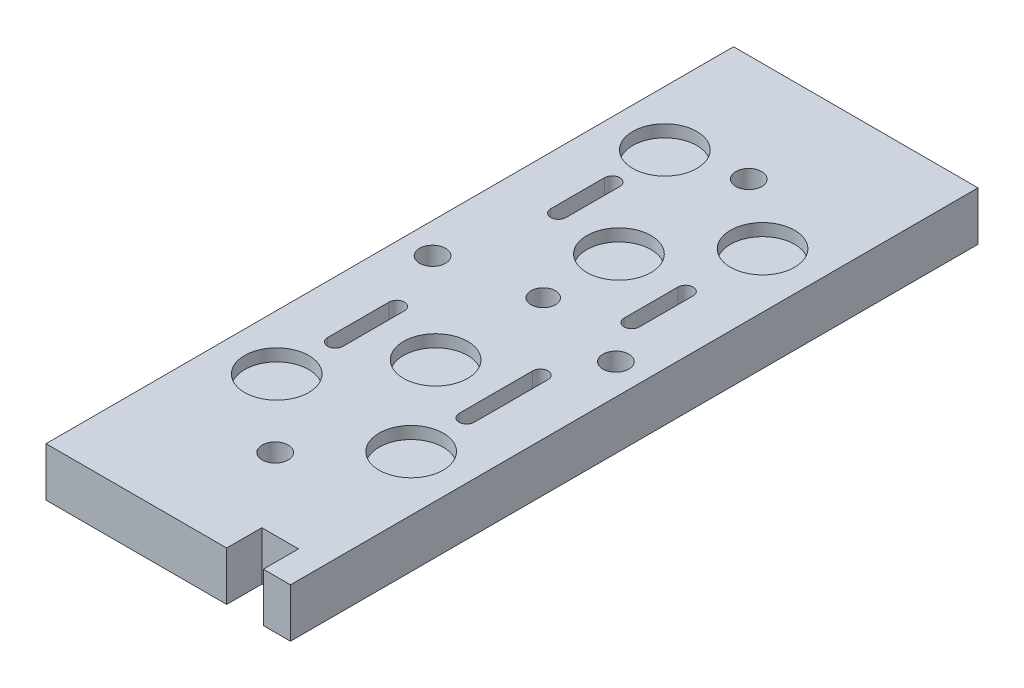
SolidWorks part; units mm, degrees
material "Plain Carbon Steel"
ref_plane "Front Plane" through (0, 0, 0) normal (0, 0, 1) x (1, 0, 0)
ref_plane "Top Plane" through (0, 0, 0) normal (0, 1, 0) x (1, 0, 0)
ref_plane "Right Plane" through (0, 0, 0) normal (1, 0, 0) x (0, 0, -1)
sketch "Sketch1" plane through (0, 0, 0) normal (0, 1, 0) x (1, 0, 0)
  line L1 (-40, -112.5) -> (40, -112.5)
  line L2 (-40, -112.5) -> (-40, 112.5)
  line L3 (-40, 112.5) -> (40, 112.5)
  line L4 (40, -112.5) -> (40, 112.5)
  line L5 (-40, -112.5) -> (40, 112.5) construction
  line L6 (-40, 112.5) -> (40, -112.5) construction
  point P0 (0, 0)
  dimension "D1" = 225
  dimension "D2" = 80
extrude "Boss-Extrude1" add sketch "Sketch1" against normal blind 16
sketch "Sketch2" plane through (0, 0, 0) normal (0, 1, 0) x (1, 0, 0)
  line L4 (24, 17.68) -> (24, 35.28)
  line L5 (19, 35.28) -> (19, 17.68)
  line L6 (24, 17.68) -> (24, 35.28)
  line L7 (19, 35.28) -> (19, 17.68)
  line L10 (24, -36.32) -> (24, -12.22)
  line L11 (19, -12.22) -> (19, -36.32)
  line L12 (24, -36.32) -> (24, -12.22)
  line L13 (19, -12.22) -> (19, -36.32)
  line L16 (-24, -16.22) -> (-24, -36.32)
  line L17 (-19, -36.32) -> (-19, -16.22)
  line L18 (-24, -16.22) -> (-24, -36.32)
  line L19 (-19, -36.32) -> (-19, -16.22)
  line L22 (-24, 54.28) -> (-24, 36.68)
  line L23 (-19, 36.68) -> (-19, 54.28)
  line L24 (-24, 54.28) -> (-24, 36.68)
  line L25 (-19, 36.68) -> (-19, 54.28)
  arc A4 (24, 35.28) -> (19, 35.28) centre (21.5, 35.28) ccw
  arc A5 (19, 17.68) -> (24, 17.68) centre (21.5, 17.68) ccw
  arc A6 (24, 35.28) -> (19, 35.28) centre (21.5, 35.28) ccw
  arc A7 (19, 17.68) -> (24, 17.68) centre (21.5, 17.68) ccw
  arc A10 (24, -12.22) -> (19, -12.22) centre (21.5, -12.22) ccw
  arc A11 (19, -36.32) -> (24, -36.32) centre (21.5, -36.32) ccw
  arc A12 (24, -12.22) -> (19, -12.22) centre (21.5, -12.22) ccw
  arc A13 (19, -36.32) -> (24, -36.32) centre (21.5, -36.32) ccw
  arc A16 (-24, -36.32) -> (-19, -36.32) centre (-21.5, -36.32) ccw
  arc A17 (-19, -16.22) -> (-24, -16.22) centre (-21.5, -16.22) ccw
  arc A18 (-24, -36.32) -> (-19, -36.32) centre (-21.5, -36.32) ccw
  arc A19 (-19, -16.22) -> (-24, -16.22) centre (-21.5, -16.22) ccw
  arc A22 (-24, 36.68) -> (-19, 36.68) centre (-21.5, 36.68) ccw
  arc A23 (-19, 54.28) -> (-24, 54.28) centre (-21.5, 54.28) ccw
  arc A24 (-24, 36.68) -> (-19, 36.68) centre (-21.5, 36.68) ccw
  arc A25 (-19, 54.28) -> (-24, 54.28) centre (-21.5, 54.28) ccw
  dimension "D2" = 0.05
  dimension "D1" = 0.05
  dimension "D3" = 0.05
  dimension "D4" = 0.05
extrude "Cut-Extrude1" cut sketch "Sketch2" against normal up to next
sketch "Sketch4" plane through (0, 0, 0) normal (0, 1, 0) x (1, 0, 0)
  circle A0 centre (-22, 72) radius 10.5
  circle A1 centre (22, 60) radius 10.5
  circle A2 centre (0, 35) radius 10.5
  circle A3 centre (0, -25) radius 10.5
  circle A4 centre (22, -55) radius 10.5
  circle A5 centre (-22, -55) radius 10.5
extrude "Cut-Extrude2" cut sketch "Sketch4" against normal blind 4
sketch "Sketch5" plane through (0, -16, 0) normal (0, -1, 0) x (1, 0, 0)
  circle A0 centre (0, 100) radius 8.5
  circle A1 centre (0, -100) radius 8.5
  dimension "D1" = 17
extrude "Cut-Extrude3" cut sketch "Sketch5" against normal blind 5
sketch "Sketch6" plane through (0, 0, 0) normal (0, 1, 0) x (1, 0, 0)
  line L0 (-40, -112.5) -> (40, -112.5) construction
  line L1 (19.13, -112.5) -> (31.13, -112.5)
  line L2 (19.13, -112.5) -> (19.13, -101)
  line L3 (19.13, -101) -> (31.13, -101)
  line L4 (31.13, -112.5) -> (31.13, -101)
  line L5 (30.13, -102.5) -> (30.13, -115) construction
  line L6 (20.13, -115) -> (20.13, -102.5) construction
  line L7 (20.63, -102) -> (29.63, -102) construction
  point P8 (30.13, -108.75)
  point P11 (20.13, -108.75)
  dimension "D1" = 1
  dimension "D2" = 1
  dimension "D3" = 1
extrude "Cut-Extrude4" cut sketch "Sketch6" against normal up to next
hole_wizard "M10 Tapped Hole1" positions "Sketch9" profile "Sketch8" tap size "M10" standard "ISO" end condition through all
sketch "Sketch9" plane through (0, 0, 0) normal (0, 1, 0) x (1, 0, 0)
  point P0 (0, -77.5)
  point P2 (30, 4)
  point P4 (-30, 4)
  point P6 (0, 77.5)
  point P9 (0, 0)
  point P15 (0, 0)
  dimension "D1" = 77.5
  dimension "D2" = 77.5
  dimension "D3" = 4
  dimension "D4" = 30
  dimension "D5" = 30
sketch "Sketch8" plane through (0, 0, 77.5) normal (1, 0, 0) x (0, 0, 1)
  line L0 (0, 0) -> (0, 16)
  line L1 (0, 16) -> (4.25, 16)
  line L2 (4.25, 16) -> (4.25, 0)
  line L5 (4.25, 0) -> (0, 0)
  line L11 (0, -6.35) -> (0, 107.95) construction
  dimension "Thru Tap Drill Dia." = 8.5
  dimension "Thru Tap Drill Depth" = 16
cosmetic thread "Hole Thread1" parameters "D2"=10
cosmetic thread "Hole Thread2" parameters "D2"=10
cosmetic thread "Hole Thread3" parameters "D2"=10
cosmetic thread "Hole Thread4" parameters "D2"=10
sketch "Sketch10" plane through (0, 0, 0) normal (0, 1, 0) x (1, 0, 0)
  circle A0 centre (0, 10.23) radius 5 construction
  circle A1 centre (0, 10.23) radius 5 construction
  circle A2 centre (0, 10.23) radius 4
  dimension "D1" = 8
extrude "Cut-Extrude5" cut sketch "Sketch10" against normal up to next
